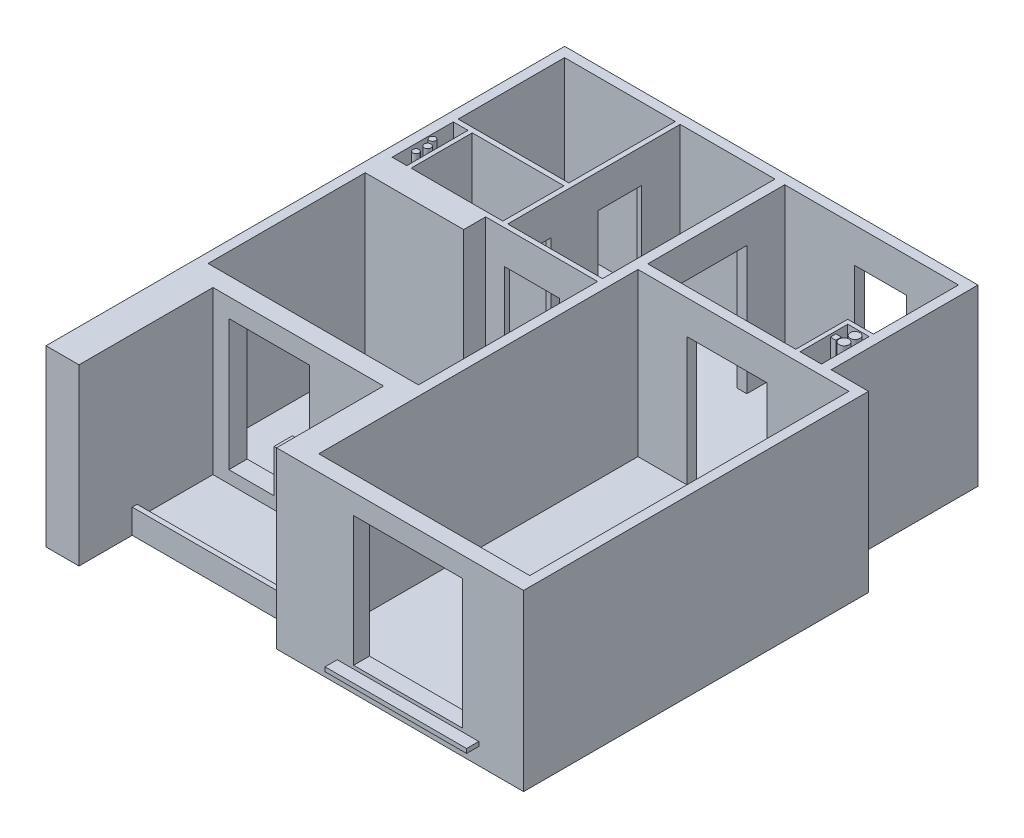
SolidWorks part; units mm, degrees
ref_plane "Спереди" through (0, 0, 0) normal (0, 0, 1) x (1, 0, 0)
ref_plane "Сверху" through (0, 0, 0) normal (0, 1, 0) x (1, 0, 0)
ref_plane "Справа" through (0, 0, 0) normal (1, 0, 0) x (0, 0, -1)
other "Configuration Table"
sketch "чертеж" plane through (0, 0, 0) normal (0, 1, 0) x (1, 0, 0)
  line L0 (-122.4645, -5934.5928) -> (200.8688, -5934.5928) construction
  line L1 (11.3792, -6202.3586) -> (334.7125, -6202.3586) construction
  line L2 (-29.7674, 42.6262) -> (294.8993, 42.6262) construction
  line L3 (-41.8231, 39.2884) -> (282.8435, 39.2884) construction
  line L4 (2418.4622, -1094.6493) -> (2743.1288, -1094.6493) construction
  line L5 (-60.4594, 42.9789) -> (264.2073, 42.9789) construction
  line L6 (-48.7728, 66.0913) -> (275.8939, 66.0913) construction
  line L7 (-42.5542, 93.9023) -> (282.1124, 93.9023) construction
  line L8 (134.2311, 87.3942) -> (458.8978, 87.3942) construction
  line L9 (-47.3906, 51.9395) -> (277.2761, 51.9395) construction
  line L10 (-66.0858, -48.647) -> (431.2475, -48.647) construction
sketch "Эскиз по чертежу" plane through (0, 0, 0) normal (0, 1, 0) x (1, 0, 0)
  line L0 (0, 0) -> (0, 8400) construction
  line L1 (0, 8400) -> (1925, 8400) construction
  line L2 (6600, 8400) -> (6600, 6000) construction
  line L4 (7200, 6000) -> (7200, 600) construction
  line L5 (7200, 600) -> (3600, 600) construction
  line L6 (3600, 600) -> (3600, 8400) construction
  line L7 (3600, 2400) -> (0, 2400) construction
  line L8 (3600, 5475) -> (0, 5475) construction
  line L32 (6600, 6000) -> (7200, 6000) construction
  line L33 (0, 870) -> (3600, 870) construction
  line L37 (0, 1050) -> (3600, 1050) construction
  line L40 (1925, 5475) -> (1925, 6550) construction
  line L42 (1925, 6550) -> (1925, 8400) construction
  line L45 (1925, 8400) -> (3600, 8400) construction
  line L46 (3600, 8400) -> (6600, 8400) construction
  line L49 (1925, 6550) -> (0, 6550) construction
  dimension "D1" = 600
  dimension "D2" = 1800
  dimension "D3" = 3600
  dimension "D4" = 1530
  dimension "D5" = 600
  dimension "D6" = 3600
  dimension "D7" = 3600
  dimension "D8" = 2400
  dimension "D9" = 2925
  dimension "D10" = 1925
  dimension "D11" = 1850
  dimension "D12" = 1350
sketch "Эскиз3" plane through (0, 0, 0) normal (0, 1, 0) x (1, 0, 0)
  line L1 (3520, 6130) -> (3680, 6130)
  line L2 (4510, 700) -> (4510, 1200) construction
  line L11 (80, 8320) -> (3520, 8320)
  line L15 (3520, 8320) -> (3520, 7700)
  line L16 (3520, 7700) -> (3680, 7700)
  line L17 (3680, 7700) -> (3680, 8320)
  line L20 (6520, 6080) -> (5790, 6080)
  line L21 (-80, 8480) -> (4820, 8480)
  line L22 (6520, 8320) -> (6520, 6080)
  line L24 (4820, 8480) -> (4820, 8320)
  line L25 (4820, 8320) -> (3680, 8320)
  line L26 (6680, 8480) -> (5670, 8480)
  line L29 (7130, 5920) -> (7130, 700)
  line L30 (4510, 700) -> (3680, 700)
  line L32 (6290, 540) -> (7290, 540)
  line L33 (7290, 540) -> (7290, 6080)
  line L34 (7290, 6080) -> (6680, 6080)
  line L35 (6680, 6080) -> (6680, 8480)
  line L39 (5670, 8480) -> (5670, 8320)
  line L40 (5670, 8320) -> (6520, 8320)
  line L41 (5790, 6080) -> (5790, 5920)
  line L42 (5790, 5920) -> (7130, 5920)
  line L45 (-80, 8480) -> (-80, 0)
  line L46 (-80, 0) -> (80, 0)
  line L47 (3680, 6080) -> (4480, 6080)
  line L52 (80, 0) -> (80, 8320)
  line L60 (3680, 700) -> (3680, 5920)
  line L68 (3520, 6130) -> (3520, 540)
  line L69 (4480, 6080) -> (4480, 5920)
  line L70 (4480, 5920) -> (3680, 5920)
  line L71 (7130, 700) -> (6290, 700)
  line L72 (6290, 540) -> (6290, 700)
  line L73 (3520, 540) -> (4510, 540)
  line L74 (4510, 540) -> (4510, 700)
  line L76 (4510, 1200) -> (3680, 1200) construction
  line L77 (6290, 700) -> (6290, 1200) construction
  line L78 (4510, 1200) -> (6290, 1200) construction
  line L79 (6290, 1200) -> (7130, 1200) construction
  line L80 (3680, 6130) -> (3680, 6080)
  line L81 (3600, 8400) -> (6600, 8400) construction
  line L83 (0, 0) -> (0, 8400) construction
  dimension "D1" = 3440
  dimension "D2" = 3450
  dimension "D3" = 5220
  dimension "D4" = 1340
  dimension "D5" = 160
  dimension "D6" = 2840
  dimension "D7" = 160
  dimension "D8" = 160
  dimension "D9" = 2240
  dimension "D10" = 160
  dimension "D11" = 80
  dimension "D12" = 160
  dimension "D13" = 160
  dimension "D14" = 80
  dimension "D15" = 1140
  dimension "D16" = 160
  dimension "D17" = 850
  dimension "D18" = 620
  dimension "D19" = 160
  dimension "D20" = 800
  dimension "D21" = 840
  dimension "D22" = 500
  dimension "D23" = 50
  dimension "D24" = 830
  dimension "D25" = 850
  dimension "D26" = 1310
  dimension "D27" = 730
  dimension "D28" = 1570
  dimension "D29" = 1780
extrude "несущие стены" add sketch "Эскиз3" along normal blind 2650 separate body
sketch "Эскиз8" plane through (0, 0, 0) normal (0, 1, 0) x (1, 0, 0)
  line L0 (80, 8320) -> (3520, 8320) construction
  line L1 (80, 5500) -> (1690, 5500)
  line L2 (80, 5500) -> (80, 5060)
  line L3 (80, 5060) -> (1690, 5060)
  line L4 (1690, 5500) -> (1690, 5060)
  line L10 (80, 0) -> (80, 8320) construction
  dimension "D1" = 440
  dimension "D2" = 2820
  dimension "D5" = 1610
extrude "вытяжка кухня" add sketch "Эскиз8" along normal up to surface (2650 mm away) up to face at (6481.4286, 2650, -5160)
sketch "Эскиз5" plane through (0, 0, 0) normal (0, 1, 0) x (1, 0, 0)
  line L0 (80, 6580) -> (1890, 6580)
  line L1 (1970, 6210) -> (1970, 5500) construction
  line L2 (1890, 6580) -> (1890, 6980)
  line L3 (1890, 6980) -> (1970, 6980)
  line L4 (1970, 6980) -> (1970, 6210)
  line L5 (1970, 6210) -> (1890, 6210)
  line L6 (1890, 6210) -> (1890, 6500)
  line L7 (1890, 6500) -> (80, 6500)
  line L9 (80, 6500) -> (80, 6580)
  line L10 (1690, 5420) -> (2000, 5420)
  line L12 (2000, 5420) -> (2000, 5500)
  line L17 (2000, 5500) -> (1690, 5500)
  line L18 (1690, 5500) -> (1690, 5420)
  line L19 (3520, 5420) -> (2900, 5420)
  line L20 (3520, 6130) -> (3520, 540) construction
  line L21 (2900, 5420) -> (2900, 5500)
  line L22 (2900, 5500) -> (3520, 5500)
  line L23 (80, 0) -> (80, 5060) construction
  line L24 (3520, 5500) -> (3520, 5420)
  line L25 (1890, 8320) -> (1890, 7690)
  line L26 (1690, 5060) -> (1690, 5500) construction
  line L27 (1890, 7690) -> (1970, 7690)
  line L28 (1970, 7690) -> (1970, 8320)
  line L30 (1970, 8320) -> (1890, 8320)
  line L31 (80, 8320) -> (3520, 8320) construction
  line L32 (3520, 8320) -> (3520, 7700) construction
  point P12 (2000, 5460)
  point P14 (2900, 5460)
  dimension "D1" = 630
  dimension "D2" = 1810
  dimension "D3" = 1550
  dimension "D4" = 1740
  dimension "D5" = 80
  dimension "D6" = 400
  dimension "D7" = 770
  dimension "D8" = 1000
  dimension "D9" = 310
  dimension "D10" = 30
  dimension "D11" = 80
  dimension "D12" = 80
  dimension "D13" = 710
  dimension "D14" = 290
  dimension "D15" = 620
  dimension "D16" = 900
  dimension "D17" = 710
extrude "перегородки санузла" add sketch "Эскиз5" along normal up to surface (2650 mm away) up to face at (1970, 2650, -6197.1429)
sketch "Эскиз9" plane through (0, 0, 0) normal (0, 1, 0) x (1, 0, 0)
  line L0 (320, 6500) -> (390, 6500)
  line L1 (6520, 6930) -> (6100, 6930)
  line L4 (6100, 6930) -> (6100, 6080)
  line L5 (80, 6500) -> (1890, 6500) construction
  line L6 (6520, 6080) -> (5790, 6080) construction
  line L7 (6170, 6860) -> (6520, 6860)
  line L8 (6170, 6860) -> (6170, 6080)
  line L11 (6520, 8320) -> (6520, 6080) construction
  line L13 (390, 5500) -> (320, 5500)
  line L14 (390, 6500) -> (390, 5500)
  line L15 (2000, 5500) -> (80, 5500) construction
  line L19 (320, 6500) -> (320, 5500)
  line L22 (1890, 6500) -> (1890, 6210) construction
  line L23 (5790, 6080) -> (5790, 5920) construction
  line L24 (6520, 6930) -> (6520, 6860)
  line L25 (6100, 6080) -> (6170, 6080)
  line L26 (6390, 6580) -> (6390, 6080) construction
  line L27 (6390, 6580) -> (6390, 6760) construction
  line L28 (6390, 6760) -> (6520, 6760) construction
  line L29 (6300, 6580) -> (6310, 6580) construction
  line L30 (6210, 6625) -> (6300, 6625)
  line L31 (6210, 6625) -> (6210, 6535)
  line L32 (6210, 6535) -> (6300, 6535)
  line L33 (190, 5780) -> (190, 5500) construction
  line L34 (150, 6090) -> (150, 6500) construction
  line L35 (150, 6090) -> (80, 6090) construction
  line L36 (190, 5780) -> (80, 5780) construction
  line L37 (80, 5500) -> (80, 6500) construction
  line L38 (210, 5950) -> (80, 5950) construction
  line L39 (210, 5950) -> (210, 5500) construction
  line L40 (6300, 6625) -> (6300, 6535)
  line L41 (5670, 8320) -> (6520, 8320) construction
  circle A0 centre (6390, 6760) radius 80
  circle A1 centre (6390, 6580) radius 80
  circle A2 centre (150, 6090) radius 50
  circle A3 centre (210, 5950) radius 55
  circle A4 centre (190, 5780) radius 50
  point P13 (6310, 6930)
  point P23 (6390, 6500)
  dimension "D5" = 130
  dimension "D10" = 310
  dimension "D12" = 100
  dimension "D15" = 110
  dimension "D16" = 110
  dimension "D9" = 160
  dimension "D1" = 850
  dimension "D2" = 70
  dimension "D3" = 310
  dimension "D4" = 420
  dimension "D6" = 500
  dimension "D7" = 680
  dimension "D8" = 70
  dimension "D11" = 1500
  dimension "D13" = 280
  dimension "D14" = 310
  dimension "D17" = 130
  dimension "D18" = 450
  dimension "D19" = 410
  dimension "D20" = 70
  dimension "D21" = 90
  dimension "D22" = 10
  dimension "D23" = 1390
extrude "зсс" add sketch "Эскиз9" along normal up to surface (2650 mm away) up to face at (6481.4286, 2650, -5160)
sketch "Эскиз7" plane through (0, 0, 0) normal (0, 1, 0) x (1, 0, 0)
  line L0 (80, 0) -> (80, 5060) construction
  line L1 (720, 2490) -> (80, 2490)
  line L2 (460, 2190) -> (460, 0)
  line L3 (3250, 2190) -> (3250, 440)
  line L4 (3250, 440) -> (4510, 440)
  line L5 (460, 0) -> (80, 0)
  line L6 (80, 2490) -> (80, 0)
  line L7 (80, 0) -> (80, 5060) construction
  line L8 (3250, 2190) -> (2040, 2190)
  line L9 (3520, 540) -> (4510, 540) construction
  line L10 (2040, 2490) -> (3520, 2490)
  line L19 (4510, 540) -> (4510, 440)
  line L20 (6290, 540) -> (7290, 540)
  line L21 (6290, 540) -> (6290, 440)
  line L22 (6290, 440) -> (7290, 440)
  line L23 (7290, 540) -> (7290, 440)
  line L24 (2040, 2190) -> (2040, 2490)
  line L25 (3520, 2490) -> (3520, 540)
  line L26 (3520, 540) -> (4510, 540)
  line L27 (3520, 5420) -> (3520, 540) construction
  line L28 (6290, 540) -> (7290, 540) construction
  line L29 (460, 2190) -> (720, 2190)
  line L30 (720, 2190) -> (720, 2490)
  line L31 (4510, 540) -> (4510, 700) construction
  line L32 (6290, 700) -> (6290, 540) construction
  line L34 (2900, 5420) -> (3520, 5420) construction
  line L35 (80, 5060) -> (1690, 5060) construction
  line L36 (3520, 5420) -> (3520, 540) construction
  point P31 (720, 2340)
  dimension "D1" = 2790
  dimension "D2" = 100
  dimension "D3" = 2930
  dimension "D4" = 2570
  dimension "D5" = 1480
  dimension "D6" = 1210
  dimension "D7" = 260
  dimension "D8" = 640
  dimension "D9" = 300
extrude "лоджия" add sketch "Эскиз7" along normal up to surface (2650 mm away) up to face at (1842.1429, 2650, -6505.7143)
sketch "Эскиз11" plane through (0, 0, 0) normal (0, 1, 0) x (1, 0, 0)
  line L1 (2040, 2490) -> (1460, 2490)
  line L2 (2040, 2490) -> (2040, 2190)
  line L3 (2040, 2190) -> (1460, 2190)
  line L4 (1460, 2490) -> (1460, 2190)
  line L5 (720, 2190) -> (720, 2490) construction
  dimension "D1" = 740
  dimension "D2" = 580
extrude "лоджияперегородка" add sketch "Эскиз11" along normal blind 900
sketch "Эскиз4" plane through (0, 0, 0) normal (0, 1, 0) x (1, 0, 0)
  line L8 (-80, 8480) -> (6680, 8480)
  line L9 (6680, 8480) -> (6680, 6080)
  line L10 (6680, 6080) -> (7290, 6080)
  line L11 (7290, 6080) -> (7290, 440)
  line L13 (3250, 440) -> (3250, 870)
  line L14 (3250, 870) -> (460, 870)
  line L17 (-80, 0) -> (-80, 8480)
  line L18 (6680, 6080) -> (6680, 8480) construction
  line L19 (6680, 8480) -> (5670, 8480) construction
  line L20 (460, 950) -> (3250, 950) construction
  line L21 (460, 0) -> (460, 2190) construction
  line L22 (3250, 2190) -> (3250, 440) construction
  line L24 (460, 870) -> (460, 0)
  line L25 (460, 0) -> (-80, 0)
  line L26 (3250, 440) -> (7290, 440)
  line L27 (2040, 2190) -> (3250, 2190) construction
  line L28 (460, 0) -> (460, 2190) construction
  line L29 (-80, 0) -> (460, 0) construction
  dimension "D1" = 80
  dimension "D2" = 1240
extrude "пол" add sketch "Эскиз4" against normal blind 200
sketch "Эскиз49" plane through (0, 0, 0) normal (0, 1, 0) x (1, 0, 0)
  line L0 (460, 0) -> (460, 2190) construction
  line L1 (3250, 870) -> (460, 870)
  line L2 (3250, 870) -> (3250, 950)
  line L3 (3250, 950) -> (460, 950)
  line L4 (460, 870) -> (460, 950)
  dimension "D1" = 80
extrude "лоджиябордюрподокно" add sketch "Эскиз49" along normal blind 200
sketch "Эскиз50" plane through (0, 0, -440) normal (0, 0, 1) x (1, 0, 0)
  line L0 (4510, 0) -> (6290, 0) construction
  line L1 (4242.5, 145) -> (6557.5, 145)
  line L2 (4242.5, 145) -> (4242.5, 75)
  line L3 (4242.5, 75) -> (6557.5, 75)
  line L4 (6557.5, 145) -> (6557.5, 75)
  line L5 (5400, 0) -> (5400, 75) construction
  point P4 (5400, 75)
  point P5 (5400, 0)
  dimension "D1" = 70
  dimension "D2" = 2315
  dimension "D3" = 75
sketch "Эскиз54" plane through (0, 0, 0) normal (0, 1, 0) x (1, 0, 0)
  line L1 (720, 2490) -> (1460, 2490)
  line L2 (720, 2490) -> (720, 2190)
  line L3 (720, 2190) -> (1460, 2190)
  line L4 (1460, 2490) -> (1460, 2190)
extrude "лоджиябордюрподдверь" add sketch "Эскиз54" along normal blind 200
sketch "Эскиз51" plane through (0, 0, 0) normal (0, 1, 0) x (1, 0, 0)
  line L0 (4510, 440) -> (4510, 700) construction
  line L1 (6290, 440) -> (4510, 440)
  line L2 (6290, 440) -> (6290, 700)
  line L3 (6290, 700) -> (4510, 700)
  line L4 (4510, 440) -> (4510, 700)
extrude "залбордярподконо" add sketch "Эскиз51" along normal blind 200
extrude "подоконникнаружний" add sketch "Эскиз50" along normal blind 200
sketch "Эскиз53" plane through (0, 2650, 0) normal (0, 1, 0) x (1, 0, 0)
  line L1 (2040, 2490) -> (720, 2490)
  line L2 (2040, 2490) -> (2040, 2190)
  line L3 (2040, 2190) -> (720, 2190)
  line L4 (720, 2490) -> (720, 2190)
extrude "лоджияверх" add sketch "Эскиз53" against normal blind 310
sketch "Эскиз52" plane through (0, 2650, 0) normal (0, 1, 0) x (1, 0, 0)
  line L1 (4510, 440) -> (6290, 440)
  line L2 (4510, 440) -> (4510, 700)
  line L3 (4510, 700) -> (6290, 700)
  line L4 (6290, 440) -> (6290, 700)
extrude "залокноверх" add sketch "Эскиз52" against normal blind 330
sketch "Эскиз55" plane through (0, 2650, 0) normal (0, 1, 0) x (1, 0, 0)
  line L1 (4820, 8480) -> (5670, 8480)
  line L2 (4820, 8480) -> (4820, 8320)
  line L3 (4820, 8320) -> (5670, 8320)
  line L4 (5670, 8480) -> (5670, 8320)
extrude "входнаядверьверх" add sketch "Эскиз55" against normal blind 570
sketch "Эскиз65" plane through (0, 2650, 0) normal (0, 1, 0) x (1, 0, 0)
  line L0 (2000, 5500) -> (390, 5500) construction
  line L1 (1890, 6210) -> (1970, 6210)
  line L2 (1890, 6210) -> (1890, 5500)
  line L3 (1890, 5500) -> (1970, 5500)
  line L4 (1970, 6210) -> (1970, 5500)
  line L6 (1890, 7690) -> (1970, 7690)
  line L7 (1890, 7690) -> (1890, 6980)
  line L8 (1890, 6980) -> (1970, 6980)
  line L9 (1970, 7690) -> (1970, 6980)
  line L10 (3520, 7700) -> (3680, 7700)
  line L11 (3520, 7700) -> (3520, 6130)
  line L12 (3520, 6130) -> (3680, 6130)
  line L13 (3680, 7700) -> (3680, 6130)
  line L14 (2000, 5500) -> (2900, 5500)
  line L15 (2000, 5500) -> (2000, 5420)
  line L16 (2000, 5420) -> (2900, 5420)
  line L17 (2900, 5500) -> (2900, 5420)
  line L18 (4480, 6080) -> (5790, 6080)
  line L19 (4480, 6080) -> (4480, 5920)
  line L20 (4480, 5920) -> (5790, 5920)
  line L21 (5790, 6080) -> (5790, 5920)
extrude "остальные" add sketch "Эскиз65" against normal offset from surface (550 mm away) 2100 up to face at (3285.8333, 0, -6273.75)
sketch "Эскиз73" [suppressed] plane through (0, 0, 0) normal (0, 1, 0) x (1, 0, 0)
  line L0 (3520, 2490) -> (80, 2490) construction
  line L1 (80, 5060) -> (1970, 5060)
  line L2 (80, 5060) -> (80, 2490)
  line L3 (80, 2490) -> (720, 2490)
  line L4 (720, 4460) -> (720, 2490)
  line L5 (80, 3090) -> (720, 3090) construction
  line L6 (3520, 2490) -> (2620, 2490)
  line L7 (3520, 2490) -> (3520, 4490)
  line L8 (3520, 4490) -> (2620, 4490)
  line L9 (2620, 2490) -> (2620, 4490)
  line L10 (80, 4460) -> (720, 4460) construction
  line L11 (1970, 5060) -> (1970, 4460)
  line L12 (1872.0394, 3492.1247) -> (2472.0394, 3492.1247)
  line L13 (1872.0394, 3492.1247) -> (1872.0394, 2492.1247)
  line L14 (1872.0394, 2492.1247) -> (2472.0394, 2492.1247)
  line L15 (2472.0394, 3492.1247) -> (2472.0394, 2492.1247)
  line L16 (1970, 4460) -> (720, 4460)
  line L17 (1970, 6210) -> (1970, 5060) construction
  line L20 (720, 4460) -> (720, 5060) construction
  line L21 (1370, 4460) -> (1370, 5060) construction
  line L23 (121.4231, 3440) -> (671.4231, 3440)
  line L24 (121.4231, 3440) -> (121.4231, 3140)
  line L25 (121.4231, 3140) -> (671.4231, 3140)
  line L26 (671.4231, 3440) -> (671.4231, 3140)
  line L27 (176.255, 4410) -> (626.255, 4410)
  line L28 (176.255, 4410) -> (176.255, 3960)
  line L29 (176.255, 3960) -> (626.255, 3960)
  line L30 (626.255, 4410) -> (626.255, 3960)
  dimension "D2" = 900
  dimension "D3" = 2000
  dimension "D4" = 600
  dimension "D5" = 600
  dimension "D6" = 50
  dimension "D7" = 1000
  dimension "D8" = 600
  dimension "D10" = 600
  dimension "D12" = 550
  dimension "D13" = 300
  dimension "D14" = 50
  dimension "D15" = 520
  dimension "D16" = 650
  dimension "D17" = 450
  dimension "D18" = 450
sketch "Эскиз47" [suppressed] plane through (0, 0, 0) normal (0, 1, 0) x (1, 0, 0)
  line L0 (3520, 5420) -> (3520, 2490) construction
  line L1 (1690, 6500) -> (3520, 6500) construction
  line L2 (1690, 6500) -> (1690, 4300) construction
  line L3 (1690, 4300) -> (3520, 4300) construction
  line L4 (3520, 6500) -> (3520, 4300) construction
  line L5 (1610, 5060) -> (1610, 6580) construction
  line L6 (390, 6500) -> (1890, 6500) construction
  line L7 (1690, 5060) -> (1690, 5420) construction
  line L9 (1970, 7720) -> (1970, 8320) construction
  line L10 (1890, 6580) -> (80, 6580) construction
  line L11 (1890, 8320) -> (1970, 8320)
  line L12 (1890, 8320) -> (1890, 6580)
  line L13 (1610, 6580) -> (1690, 6580) construction
  line L14 (1690, 6580) -> (1690, 6500) construction
  line L15 (1890, 6580) -> (1970, 6580)
  line L16 (1970, 8320) -> (1970, 6580)
  line L17 (3520, 5420) -> (3520, 2490) construction
  line L18 (3520, 3790) -> (3680, 3790)
  line L19 (3520, 3790) -> (3520, 3090)
  line L20 (3520, 3090) -> (3680, 3090)
  line L21 (3680, 3790) -> (3680, 3090)
  line L22 (3680, 700) -> (3680, 5920) construction
  line L23 (1890, 7020) -> (1890, 6580) construction
  line L24 (3520, 2490) -> (80, 2490) construction
  line L25 (1970, 6200) -> (1970, 7020) construction
  line L26 (390, 6500) -> (1610, 6500)
  line L27 (390, 6500) -> (390, 6580)
  line L28 (390, 6580) -> (1610, 6580)
  line L29 (1610, 6500) -> (1610, 6580)
  line L30 (3520, 5500) -> (1690, 5500)
  line L31 (3520, 5500) -> (3520, 5420)
  line L32 (3520, 5420) -> (1690, 5420)
  line L33 (1690, 5500) -> (1690, 5420)
  line L34 (1890, 6500) -> (1970, 6500)
  line L35 (1890, 6500) -> (1890, 6200)
  line L36 (1890, 6200) -> (1970, 6200)
  line L37 (1970, 6500) -> (1970, 6200)
  line L38 (1970, 5500) -> (1970, 8320) construction
  line L39 (80, 5060) -> (1690, 5060) construction
  dimension "D1" = 700
  dimension "D2" = 2200
  dimension "D3" = 600
extrude "Вырез-Вытянуть3" [suppressed] cut sketch "Эскиз47" along normal blind 2000
sketch "Эскиз48" [suppressed] plane through (0, 0, 0) normal (0, 1, 0) x (1, 0, 0)
  line L0 (5830, 5920) -> (7130, 5920) construction
  line L1 (1610, 6500) -> (1690, 6500)
  line L2 (1610, 6500) -> (1610, 5500)
  line L3 (1610, 5500) -> (1690, 5500)
  line L4 (1690, 6500) -> (1690, 5500)
  line L5 (5830, 6080) -> (5395, 6080)
  line L6 (5830, 6080) -> (5830, 5920)
  line L7 (5830, 5920) -> (5395, 5920)
  line L8 (5395, 6080) -> (5395, 5920)
  line L10 (3520, 6130) -> (3520, 3790) construction
  line L11 (3680, 6580) -> (3680, 6130)
  line L12 (1970, 6500) -> (3520, 6500)
  line L13 (3520, 6500) -> (3520, 6130)
  line L14 (3520, 6130) -> (3680, 6130)
  line L15 (3520, 6080) -> (3520, 3790) construction
  line L16 (3680, 6080) -> (3680, 6130) construction
  line L17 (3680, 700) -> (3680, 5920) construction
  line L18 (1970, 6500) -> (1970, 6580)
  line L19 (3680, 7720) -> (3520, 7720)
  line L20 (3520, 7720) -> (3520, 7280)
  line L21 (3520, 7280) -> (3680, 7280)
  line L22 (3680, 7280) -> (3680, 7720)
  line L23 (3680, 6580) -> (1970, 6580)
  line L24 (3680, 3790) -> (3520, 3790) construction
  line L25 (3680, 4040) -> (5330, 4040) construction
  line L26 (3680, 4040) -> (3680, 3940) construction
  line L27 (3680, 3940) -> (5330, 3940) construction
  line L28 (5330, 4040) -> (5330, 3940) construction
  line L29 (7130, 5920) -> (7130, 700) construction
  line L30 (5395, 8320) -> (5395, 6080) construction
  line L31 (4530, 5920) -> (4530, 6080) construction
  line L32 (3520, 6130) -> (3520, 3790) construction
  dimension "D1" = 865
  dimension "D2" = 700
  dimension "D3" = 100
  dimension "D4" = 150
  dimension "D5" = 1800
extrude "Бобышка-Вытянуть34" [suppressed] add sketch "Эскиз48" along normal through all
sketch "Эскиз60" [suppressed] plane through (0, 0, 0) normal (0, 1, 0) x (1, 0, 0)
  line L0 (1610, 5500) -> (390, 5500) construction
  line L1 (390, 6580) -> (550, 6580)
  line L2 (390, 6580) -> (390, 5500)
  line L3 (390, 5500) -> (550, 5500)
  line L4 (550, 6580) -> (550, 5500)
  line L5 (390, 5500) -> (390, 6580) construction
  dimension "D1" = 160
extrude "утолщениедлядуша" [suppressed] add sketch "Эскиз60" along normal up to surface (2640 mm away) up to face at (5433.3333, 2650, -7110)
sketch "Эскиз61" [suppressed] plane through (0, 0, 0) normal (0, 1, 0) x (1, 0, 0)
  line L0 (1890, 6580) -> (80, 6580) construction
  line L1 (1890, 8320) -> (1970, 8320)
  line L2 (1890, 8320) -> (1890, 6580)
  line L3 (1890, 6210) -> (1970, 6210)
  line L4 (1970, 8320) -> (1970, 6210)
  line L5 (3520, 5500) -> (1690, 5500)
  line L6 (3520, 5500) -> (3520, 5420)
  line L7 (3520, 5420) -> (1690, 5420)
  line L8 (1690, 5500) -> (1690, 5420)
  line L9 (390, 6500) -> (1890, 6500)
  line L10 (390, 6500) -> (390, 6580)
  line L11 (390, 6580) -> (1890, 6580)
  line L13 (1890, 6500) -> (1890, 6210)
extrude "Вырез-Вытянуть4" [suppressed] cut sketch "Эскиз61" along normal up to surface (2640 mm away) up to face at (5433.3333, 2650, -7110)
sketch "Эскиз62" [suppressed] plane through (0, 0, 0) normal (0, 1, 0) x (1, 0, 0)
  line L0 (7130, 5920) -> (7130, 700) construction
  line L1 (5130, 2900) -> (7130, 2900)
  line L2 (5130, 2900) -> (5130, 1400)
  line L3 (5130, 1400) -> (7130, 1400)
  line L4 (7130, 2900) -> (7130, 1400)
  line L5 (5790, 5920) -> (7130, 5920) construction
  line L9 (3680, 5920) -> (4480, 5920)
  line L11 (4680, 3600) -> (4680, 3680)
  line L12 (3680, 3680) -> (3880, 3680)
  line L13 (3680, 700) -> (3680, 5920) construction
  line L14 (7130, 1400) -> (7130, 700) construction
  line L15 (3880, 3680) -> (3880, 3600)
  line L16 (3880, 3600) -> (3680, 3600)
  line L17 (3680, 700) -> (3680, 5920) construction
  line L18 (3680, 3600) -> (3680, 3680)
  line L19 (4680, 3680) -> (4880, 3680)
  line L20 (4880, 3680) -> (4880, 4600)
  line L22 (7130, 4600) -> (7130, 4520)
  line L23 (7130, 5920) -> (7130, 700) construction
  line L24 (7130, 4520) -> (4960, 4520)
  line L25 (4960, 4520) -> (4960, 3600)
  line L26 (4680, 3600) -> (4960, 3600)
  line L27 (4960, 3600) -> (7130, 3600) construction
  line L28 (4880, 3680) -> (4960, 3680) construction
  line L29 (7130, 3600) -> (7130, 2900) construction
  line L30 (3680, 5920) -> (3680, 6080)
  line L31 (3880, 3600) -> (4680, 3600) construction
  line L32 (7130, 4600) -> (4880, 4600)
  line L36 (7130, 5920) -> (7130, 4600) construction
  line L37 (5790, 5920) -> (7130, 5920) construction
  line L38 (3680, 3680) -> (3680, 4480)
  line L39 (3680, 4480) -> (3520, 4480)
  line L40 (3520, 6130) -> (3520, 2490) construction
  line L41 (3520, 4480) -> (3520, 3680)
  line L42 (3520, 6130) -> (3520, 2490) construction
  line L43 (3520, 3680) -> (3680, 3680)
  line L44 (3680, 6080) -> (4480, 6080)
  line L45 (4480, 5920) -> (4480, 6080)
  line L46 (7130, 4650) -> (6330, 4650)
  line L47 (7130, 4650) -> (7130, 5920)
  line L48 (7130, 5920) -> (6330, 5920)
  line L49 (6330, 4650) -> (6330, 5920)
  line L50 (3520, 8320) -> (3520, 7700) construction
  line L55 (3680, 7150) -> (1690, 7150)
  line L57 (3680, 7700) -> (3680, 7150)
  line L58 (1690, 5500) -> (1540, 5500)
  line L60 (1540, 7300) -> (3520, 7300)
  line L61 (3520, 7300) -> (3520, 7700)
  line L62 (3520, 7300) -> (3520, 7150) construction
  line L63 (3520, 7700) -> (3680, 7700)
  line L64 (80, 8320) -> (3520, 8320) construction
  line L65 (1690, 5060) -> (1690, 5500) construction
  line L66 (1690, 5060) -> (1690, 5500) construction
  line L67 (1690, 5500) -> (390, 5500) construction
  line L69 (1690, 7150) -> (1690, 7000)
  line L70 (1690, 7000) -> (1540, 7000)
  line L71 (1540, 7000) -> (1540, 7300)
  line L72 (1690, 5500) -> (1690, 6200)
  line L73 (1690, 6200) -> (1540, 6200)
  line L74 (1540, 6200) -> (1540, 5500)
  line L75 (3520, 4980) -> (2490, 4980)
  line L76 (3520, 6130) -> (3220, 6130)
  line L77 (3520, 6130) -> (3520, 5530)
  line L78 (3520, 5530) -> (3220, 5530)
  line L79 (3220, 6130) -> (3220, 5530)
  line L80 (2490, 4980) -> (2490, 6130)
  line L81 (2490, 6130) -> (3210, 6130)
  line L82 (3210, 6130) -> (3210, 5520)
  line L83 (3210, 5520) -> (3520, 5520)
  line L84 (3520, 5520) -> (3520, 4980)
  line L85 (3210, 6130) -> (3220, 6130) construction
  line L86 (3520, 5520) -> (3520, 5530) construction
  line L88 (80, 5060) -> (680, 5060)
  line L89 (80, 5060) -> (80, 3860)
  line L90 (80, 3860) -> (680, 3860)
  line L91 (680, 5060) -> (680, 3860)
  point P72 (1615, 6200)
  dimension "D12" = 300
  dimension "D1" = 2000
  dimension "D2" = 1500
  dimension "D3" = 700
  dimension "D4" = 800
  dimension "D5" = 80
  dimension "D6" = 200
  dimension "D7" = 1320
  dimension "D8" = 920
  dimension "D9" = 700
  dimension "D10" = 200
  dimension "D11" = 800
  dimension "D13" = 1020
  dimension "D14" = 150
  dimension "D15" = 800
  dimension "D16" = 50
  dimension "D17" = 800
  dimension "D18" = 150
  dimension "D19" = 600
  dimension "D20" = 500
  dimension "D21" = 10
  dimension "D22" = 800
  dimension "D23" = 600
  dimension "D24" = 1200
sketch "Эскиз63" [suppressed] plane through (0, 0, 0) normal (0, 1, 0) x (1, 0, 0)
  line L1 (3680, 5920) -> (4480, 5920)
  line L2 (3680, 5920) -> (3680, 6080)
  line L3 (3680, 6080) -> (4480, 6080)
  line L4 (4480, 5920) -> (4480, 6080)
  line L5 (3680, 3680) -> (3520, 3680)
  line L6 (3680, 3680) -> (3680, 4480)
  line L7 (3680, 4480) -> (3520, 4480)
  line L8 (3520, 3680) -> (3520, 4480)
extrude "Вырез-Вытянуть6" [suppressed] cut sketch "Эскиз63" along normal through all
sketch "Эскиз64" [suppressed] plane through (0, 0, 0) normal (0, 1, 0) x (1, 0, 0)
  line L0 (4680, 3600) -> (4960, 3600)
  line L1 (3680, 3600) -> (3880, 3600)
  line L2 (3680, 3600) -> (3680, 3680)
  line L3 (3680, 3680) -> (3880, 3680)
  line L4 (3880, 3600) -> (3880, 3680)
  line L5 (4960, 3600) -> (4960, 4520)
  line L6 (4960, 4520) -> (7130, 4520)
  line L7 (7130, 4520) -> (7130, 4600)
  line L8 (7130, 4600) -> (4880, 4600)
  line L9 (4880, 4600) -> (4880, 3680)
  line L10 (4880, 3680) -> (4680, 3680)
  line L11 (4680, 3680) -> (4680, 3600)
extrude "Бобышка-Вытянуть35" [suppressed] add sketch "Эскиз64" along normal through all
sketch "Эскиз66" [suppressed] plane through (0, 0, 0) normal (0, 1, 0) x (1, 0, 0)
  line L1 (1890, 6500) -> (1970, 6500)
  line L2 (1890, 6500) -> (1890, 6210)
  line L3 (1890, 6210) -> (1970, 6210)
  line L4 (1970, 6500) -> (1970, 6210)
  line L5 (2900, 5500) -> (3520, 5500)
  line L6 (2900, 5500) -> (2900, 5420)
  line L7 (2900, 5420) -> (3520, 5420)
  line L8 (3520, 5500) -> (3520, 5420)
extrude "Вырез-Вытянуть7" [suppressed] cut sketch "Эскиз66" along normal blind 2100
sketch "Эскиз69" [suppressed] plane through (0, 0, 0) normal (0, 1, 0) x (1, 0, 0)
  line L1 (3520, 5420) -> (1970, 5420)
  line L2 (3520, 5420) -> (3520, 5500)
  line L3 (3520, 5500) -> (1970, 5500)
  line L4 (1970, 5420) -> (1970, 5500)
extrude "Вырез-Вытянуть9" [suppressed] cut sketch "Эскиз69" along normal through all
sketch "Эскиз68" [suppressed] plane through (0, 0, 0) normal (0, 1, 0) x (1, 0, 0)
  line L0 (2920, 6980) -> (2920, 6900)
  line L1 (3680, 6130) -> (3520, 6130)
  line L2 (3680, 6130) -> (3680, 6980)
  line L3 (3680, 6980) -> (2920, 6980)
  line L4 (3520, 6130) -> (3520, 6900)
  line L5 (2920, 6900) -> (3520, 6900)
  line L6 (3520, 8320) -> (3520, 2490) construction
  line L9 (1970, 6980) -> (2920, 6980) construction
  dimension "D1" = 600
  dimension "D2" = 80
extrude "Бобышка-Вытянуть36" [suppressed] add sketch "Эскиз68" along normal up to surface (2650 mm away) up to face at (5433.3333, 2650, -7110)
sketch "Эскиз67" [suppressed] plane through (0, 0, 0) normal (0, 1, 0) x (1, 0, 0)
  line L0 (3520, 6900) -> (3520, 2490) construction
  line L1 (440, 5522.7398) -> (990, 5522.7398)
  line L2 (440, 5522.7398) -> (440, 5972.7398)
  line L3 (440, 5972.7398) -> (990, 5972.7398)
  line L4 (990, 5522.7398) -> (990, 5972.7398)
  line L6 (1023.4102, 6479.7499) -> (1573.4102, 6479.7499)
  line L7 (1023.4102, 6479.7499) -> (1023.4102, 6029.7499)
  line L8 (1023.4102, 6029.7499) -> (1573.4102, 6029.7499)
  line L9 (1573.4102, 6479.7499) -> (1573.4102, 6029.7499)
  line L10 (390, 5500) -> (990, 5500)
  line L11 (390, 5500) -> (390, 6500)
  line L12 (390, 6500) -> (1970, 6500)
  line L13 (990, 5500) -> (990, 6000)
  line L14 (1970, 6500) -> (1970, 6000)
  line L15 (2920, 6900) -> (3520, 6900)
  line L16 (1970, 6000) -> (990, 6000)
  line L17 (2920, 6900) -> (2920, 6300)
  line L18 (3520, 8320) -> (3520, 6980) construction
  line L19 (2920, 6900) -> (3520, 6900)
  line L20 (2920, 6900) -> (2920, 4500)
  line L21 (2920, 4500) -> (3520, 4500)
  line L22 (3520, 6900) -> (3520, 4500)
  line L23 (2920, 6300) -> (3520, 6300)
  line L24 (3520, 6900) -> (3520, 6300)
  line L25 (3520, 5456.8348) -> (2970, 5456.8348)
  line L26 (3520, 5456.8348) -> (3520, 5156.8348)
  line L27 (3520, 5156.8348) -> (2970, 5156.8348)
  line L28 (2970, 5456.8348) -> (2970, 5156.8348)
  line L29 (3520, 4500) -> (2920, 4500)
  line L30 (3520, 4500) -> (3520, 5100)
  line L31 (3520, 5100) -> (2920, 5100)
  line L32 (2920, 4500) -> (2920, 5100)
  line L33 (2620, 4490) -> (3520, 4490)
  line L34 (902.1854, 4035.485) -> (1502.1854, 4035.485)
  line L35 (902.1854, 4035.485) -> (902.1854, 3035.485)
  line L36 (902.1854, 3035.485) -> (1502.1854, 3035.485)
  line L37 (1502.1854, 4035.485) -> (1502.1854, 3035.485)
  line L38 (2620, 4490) -> (2620, 2490)
  line L39 (2620, 2490) -> (3520, 2490)
  line L40 (3520, 4490) -> (3520, 2490)
  line L41 (2920, 6900) -> (3520, 6900) construction
  line L46 (1346.4078, 3766.5226) -> (1796.4078, 3766.5226)
  line L51 (630.0751, 3770.9808) -> (1080.0751, 3770.9808)
  line L52 (630.0751, 3770.9808) -> (630.0751, 3320.9808)
  line L53 (630.0751, 3320.9808) -> (1080.0751, 3320.9808)
  line L54 (1080.0751, 3770.9808) -> (1080.0751, 3320.9808)
  line L55 (1346.4078, 3766.5226) -> (1346.4078, 3316.5226)
  line L56 (1346.4078, 3316.5226) -> (1796.4078, 3316.5226)
  line L57 (1796.4078, 3766.5226) -> (1796.4078, 3316.5226)
  dimension "D2" = 550
  dimension "D3" = 450
  dimension "D4" = 550
  dimension "D5" = 600
  dimension "D6" = 500
  dimension "D7" = 600
  dimension "D8" = 600
  dimension "D9" = 550
  dimension "D10" = 300
  dimension "D11" = 600
  dimension "D12" = 1200
  dimension "D13" = 1000
  dimension "D14" = 600
  dimension "D15" = 2000
  dimension "D16" = 900
  dimension "D17" = 450
  dimension "D19" = 450
  dimension "D20" = 450
sketch "Эскиз70" [suppressed] plane through (0, 0, 0) normal (0, 1, 0) x (1, 0, 0)
  line L0 (1890, 8320) -> (1890, 7690) construction
  line L1 (1970, 5500) -> (3520, 5500)
  line L2 (1970, 5500) -> (1970, 5420)
  line L3 (1970, 5420) -> (3520, 5420)
  line L4 (3520, 5500) -> (3520, 5420)
  line L5 (390, 6500) -> (1890, 6500)
  line L6 (390, 6500) -> (390, 6580)
  line L7 (390, 6580) -> (1890, 6580)
  line L8 (1890, 6500) -> (1890, 6580)
  line L9 (1970, 6980) -> (1890, 6980)
  line L10 (1970, 6980) -> (1970, 8320)
  line L11 (1970, 8320) -> (1890, 8320)
  line L12 (1890, 6980) -> (1890, 8320)
  line L13 (80, 8320) -> (1890, 8320) construction
extrude "Вырез-Вытянуть10" [suppressed] cut sketch "Эскиз70" along normal through all
sketch "Эскиз71" [suppressed] plane through (0, 0, 0) normal (0, 1, 0) x (1, 0, 0)
  line L0 (80, 6580) -> (80, 8320) construction
  line L1 (1890, 6980) -> (80, 6980)
  line L2 (1890, 6980) -> (1890, 6900)
  line L3 (1890, 6900) -> (80, 6900)
  line L4 (80, 6980) -> (80, 6900)
  line L5 (1890, 6980) -> (1970, 6980) construction
extrude "Бобышка-Вытянуть37" [suppressed] add sketch "Эскиз71" along normal up to surface (2650 mm away) up to face at (5433.3333, 2650, -7110)
sketch "Эскиз72" [suppressed] plane through (0, 0, 0) normal (0, 1, 0) x (1, 0, 0)
  line L0 (3520, 8320) -> (3520, 2490) construction
  line L1 (80, 8320) -> (3520, 8320)
  line L2 (80, 8320) -> (80, 7720)
  line L3 (80, 7720) -> (3520, 7720)
  line L4 (3520, 8320) -> (3520, 7720)
  line L5 (80, 6980) -> (1970, 6980) construction
  line L6 (680, 8320) -> (680, 7720) construction
  line L7 (2920, 8320) -> (2920, 7720) construction
  line L9 (1970, 5420) -> (1970, 6980) construction
  dimension "D1" = 600
  dimension "D2" = 740
  dimension "D3" = 3440
  dimension "D4" = 600
  dimension "D5" = 600
  dimension "D6" = 1550
sketch "Эскиз74" [suppressed] plane through (0, 0, 0) normal (0, 1, 0) x (1, 0, 0)
  line L1 (1970, 5500) -> (3520, 5500)
  line L2 (1970, 5500) -> (1970, 5420)
  line L3 (1970, 5420) -> (3520, 5420)
  line L4 (3520, 5500) -> (3520, 5420)
extrude "Вырез-Вытянуть11" [suppressed] cut sketch "Эскиз74" along normal through all
sketch "Эскиз75" [suppressed] plane through (0, 0, 0) normal (0, 1, 0) x (1, 0, 0)
  line L0 (1890, 6580) -> (80, 6580) construction
  line L1 (167.5, 6580) -> (180, 6580)
  line L2 (167.5, 6580) -> (167.5, 8320)
  line L3 (167.5, 8320) -> (180, 8320)
  line L4 (180, 6580) -> (180, 8320)
  line L5 (80, 8320) -> (1890, 8320) construction
  line L6 (80, 6580) -> (80, 8320) construction
  dimension "D1" = 87.5
  dimension "D2" = 12.5
extrude "Бобышка-Вытянуть38" [suppressed] add sketch "Эскиз75" along normal up to surface (2650 mm away) up to face at (5433.3333, 2650, -7110)
sketch3d "Трехмерный эскиз1" [suppressed]
  line L0 (106, 75, -6580) -> (106, 50, -6580) construction
  line L1 (106, 75, -8294) -> (106, 127.2, -8294) construction
  line L2 (106, 50, -6580) -> (106, 0, -6580) construction
  line L3 (1890, 0, -6580) -> (180, 0, -6580) construction
  line L4 (106, 0, -6580) -> (80, 0, -6580) construction
  line L5 (80, 0, -6580) -> (80, 75, -6580) construction
  line L6 (80, 2650, -6580) -> (80, 0, -6580) construction
  line L7 (106, 75, -6580) -> (80, 75, -6580) construction
  line L8 (106, 75, -6580) -> (106, 75, -8320) construction
  line L9 (106, 75, -8320) -> (106, 127.2, -8320) construction
  line L10 (106, 127.2, -8294) -> (106, 127.2, -8320) construction
  line L11 (106, 127.2, -8294) -> (106, 75, -6580)
  line L12 (106, 127.2, -8294) -> (1206, 127.2, -8294) construction
  line L13 (1206, 127.2, -8294) -> (1206, 160.2, -8294) construction
  line L14 (106, 127.2, -8294) -> (1206, 160.2, -8294)
  dimension "D3" = 52.2
  dimension "D2" = 50
  dimension "D4" = 1740
  dimension "D5" = 1100
  dimension "D6" = 33
  dimension "D1" = 26
  dimension "D7" = 25
sweep "По траектории2" [suppressed] add path "Трехмерный эскиз1" circular profile diameter 50 parameters "D3"=50
equation "\"D3@Трехмерный эскиз1\"=\"D4@Трехмерный эскиз1\"*30/1000"
equation "\"D6@Трехмерный эскиз1\"=\"D5@Трехмерный эскиз1\"*30/1000"
